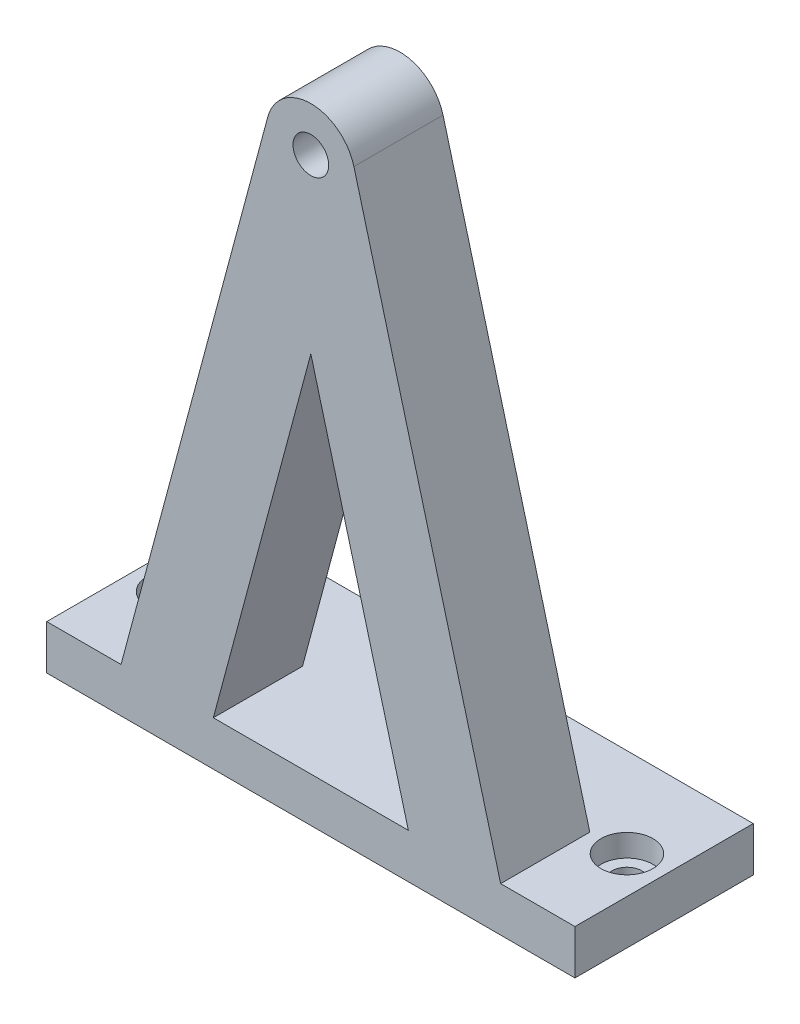
SolidWorks part; units mm, degrees
ref_plane "前视基准面" through (0, 0, 0) normal (0, 0, 1) x (1, 0, 0)
ref_plane "上视基准面" through (0, 0, 0) normal (0, 1, 0) x (1, 0, 0)
ref_plane "右视基准面" through (0, 0, 0) normal (1, 0, 0) x (0, 0, -1)
other "Configuration Table"
sketch "草图1" plane through (0, 0, 0) normal (0, 0, 1) x (1, 0, 0)
  line L3 (0, 0) -> (0, -30) construction
  line L5 (-2.8978, 0.7765) -> (-12.7733, -36.0793)
  line L6 (2.8978, 0.7765) -> (12.7733, -36.0793)
  line L8 (-6.5616, -36.0793) -> (2.8978, -0.7765)
  line L10 (6.5616, -36.0793) -> (-2.8978, -0.7765)
  line L12 (-12.7733, -36.0793) -> (-6.5616, -36.0793)
  line L13 (6.5616, -36.0793) -> (12.7733, -36.0793)
  circle A0 centre (0, 0) radius 3
  circle A6 centre (0, 0) radius 1.2
  dimension "D1" = 6
  dimension "D2" = 15
  dimension "D4" = 2.4
  dimension "D5" = 36.0793
  dimension "D3" = 15
extrude "凸台-拉伸1" add sketch "草图1" along normal blind 6 contours A0 | L6 A0 L8 L10 | L8 L10 A0 L5 | L3 A0 L10 | A0 L3 L8 | A6 region at (-1.7746, -2.3127, 0) region at (0.876, -5.5523, 0) region at (-0.876, -5.5523, 0) region at (5.758, -20.7465, 0) region at (-5.758, -20.7465, 0)
sketch "草图3" plane through (0, -36.0793, 0) normal (0, -1, 0) x (1, 0, 0)
  line L0 (6.5616, 6) -> (12.7733, 6) construction
  line L1 (17.7733, -6) -> (-17.7733, -6)
  line L2 (17.7733, -6) -> (17.7733, 6)
  line L3 (17.7733, 6) -> (-17.7733, 6)
  line L4 (-17.7733, -6) -> (-17.7733, 6)
  line L5 (6.5616, 0) -> (12.7733, 0) construction
  line L6 (12.7733, 6) -> (12.7733, 0) construction
  line L7 (-12.7733, 6) -> (-12.7733, 0) construction
  dimension "D1" = 6
  dimension "D2" = 5
  dimension "D3" = 5
extrude "凸台-拉伸2" add sketch "草图3" along normal blind 3
extrude "切除-拉伸1" cut sketch "草图1<5>" along normal through all contours A6
sketch "草图1<5>" plane through (0, 0, 0) normal (0, 0, 1) x (1, 0, 0) same geometry as "草图1"
sketch "草图4" plane through (0, -36.0793, 0) normal (0, 1, 0) x (1, 0, 0)
  line L0 (0, 0) -> (0, 6) construction
  line L1 (2.8978, 0) -> (-2.8978, 0) construction
  line L2 (-17.7733, 6) -> (17.7733, 6) construction
  line L3 (12.7733, 0) -> (17.7733, 0) construction
  line L4 (2.8978, 0) -> (12.7733, 0) construction
  line L5 (12.7733, -6) -> (12.7733, 0) construction
  line L6 (17.7733, 6) -> (17.7733, -6) construction
  line L7 (-12.7733, 0) -> (-17.7733, 0) construction
  line L8 (-2.8978, 0) -> (-12.7733, 0) construction
  line L9 (-17.7733, -6) -> (-17.7733, 6) construction
  line L10 (-12.7733, -6) -> (-12.7733, 0) construction
  circle A0 centre (15.2733, 0) radius 1.75
  circle A1 centre (-15.2733, 0) radius 1.75
  circle A2 centre (0, 3) radius 1.75
  circle A3 centre (15.2733, 0) radius 1
  circle A4 centre (0, 3) radius 1
  circle A5 centre (-15.2733, 0) radius 1
  dimension "D1" = 2
  dimension "D2" = 3.5
extrude "切除-拉伸2" cut sketch "草图4" against normal blind 1.5
extrude "切除-拉伸3" cut sketch "草图4<2>" against normal through all contours A4 | A3 | A5
sketch "草图4<2>" plane through (0, -36.0793, 0) normal (0, 1, 0) x (1, 0, 0) same geometry as "草图4"
